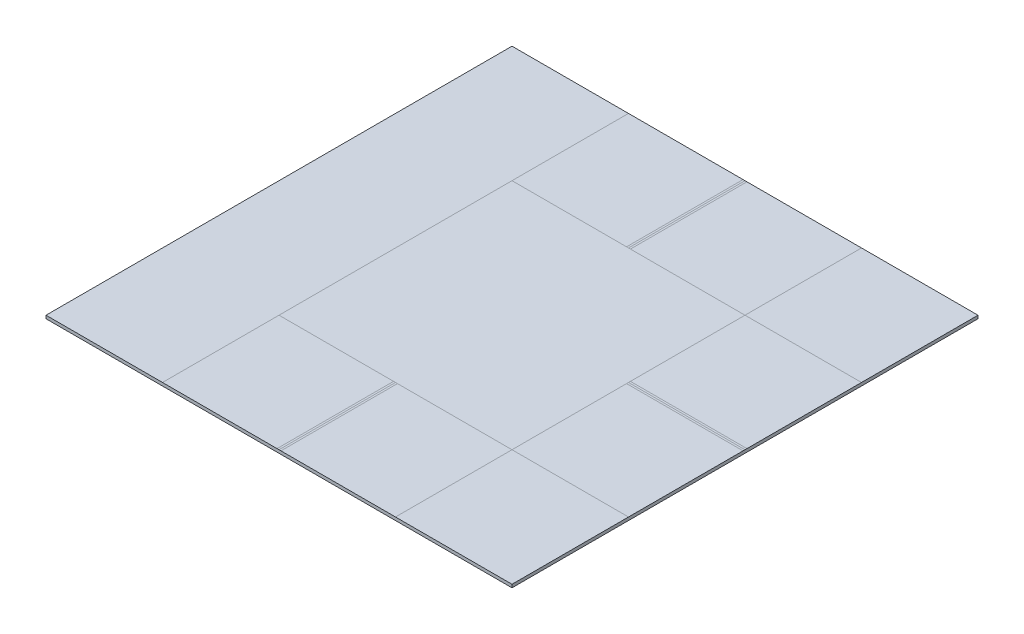
SolidWorks part; units mm, degrees
ref_plane "Front Plane" through (0, 0, 0) normal (0, 0, 1) x (1, 0, 0)
ref_plane "Top Plane" through (0, 0, 0) normal (0, 1, 0) x (1, 0, 0)
ref_plane "Right Plane" through (0, 0, 0) normal (1, 0, 0) x (0, 0, -1)
sketch "Sketch1" plane through (0, 0, 0) normal (0, 1, 0) x (1, 0, 0)
  line L0 (375, -375) -> (750, -750) construction
  line L1 (-750, -750) -> (750, -750)
  line L2 (-750, -750) -> (-750, 750)
  line L3 (-750, 750) -> (750, 750)
  line L4 (750, -750) -> (750, 750)
  line L5 (-750, -750) -> (-375, -375) construction
  line L6 (-750, 750) -> (-375, 375) construction
  line L7 (-375, -750) -> (375, -750)
  line L8 (-375, -750) -> (-375, 750)
  line L9 (-375, 750) -> (375, 750)
  line L10 (375, -750) -> (375, -375)
  line L20 (-750, 442.3995) -> (-750, -307.6005)
  line L27 (375, 375) -> (750, 375)
  line L28 (-750, 375) -> (-750, -375)
  line L29 (375, -375) -> (750, -375)
  line L30 (750, 375) -> (750, -375)
  line L31 (375, 375) -> (750, 750) construction
  line L32 (375, 375) -> (375, 750)
  point P0 (0, 0)
  point P10 (750, 0)
  point P11 (0, 750)
  dimension "D1" = 1500
  dimension "D2" = 750
extrude "Boss-Extrude1" add sketch "Sketch1" along normal blind 10 contours L1 L8 L3 L2 L20 | L27 L32 L3 L8 L1 L10 L29 L4 | L29 L10 L1 L4 | L32 L27 L4 L3 region at (-562.5, 0, 0) region at (112.5, 0, 0) region at (562.5, 0, 562.5) region at (562.5, 0, -562.5)
split line "Split Line5"
sketch "Sketch1<7>" plane through (0, 0, 0) normal (0, 1, 0) x (1, 0, 0) same geometry as "Sketch1"
ref_plane "Plane1" through (-750, 10, -750) normal (1, 0, 0) x (0, 0, -1)
sketch "Sketch3" plane through (0, 10, 0) normal (0, 1, 0) x (1, 0, 0)
  line L0 (375, 375) -> (-375, 375)
  line L1 (-375, -750) -> (-375, 750) construction
  line L2 (0, 375) -> (0, 750)
  line L3 (-375, 750) -> (375, 750) construction
  line L4 (375, -375) -> (-375, -375)
  line L5 (375, 375) -> (375, -375)
  line L6 (0, -375) -> (0, -750)
  line L7 (-375, -750) -> (375, -750) construction
  line L8 (375, 0) -> (750, 0)
  line L9 (750, -375) -> (750, 375) construction
  line L11 (-6.25, -375) -> (6.25, -375)
  line L12 (-6.25, -375) -> (-6.25, -750)
  line L13 (-6.25, -750) -> (6.25, -750)
  line L14 (6.25, -375) -> (6.25, -750)
  line L15 (-6.25, 750) -> (6.25, 750)
  line L16 (-6.25, 750) -> (-6.25, 375)
  line L17 (-6.25, 375) -> (6.25, 375)
  line L18 (6.25, 750) -> (6.25, 375)
  line L19 (375, -6.25) -> (750, -6.25)
  line L20 (375, -6.25) -> (375, 6.25)
  line L21 (375, 6.25) -> (750, 6.25)
  line L22 (750, -6.25) -> (750, 6.25)
  point P24 (0, -750)
  point P29 (0, 750)
  point P34 (750, 0)
  dimension "D1" = 12.5
  dimension "D2" = 12.5
  dimension "D3" = 12.5
split line "Split Line8"
equation "\"Scale\"= 8"
equation "\"Tile Size\"= \"Road Size\" * 2"
equation "\"D1@Sketch1\"=\"Tile Size\""
equation "\"Road Size\"= \"Real Lane Size\" * 2 / \"Scale\""
equation "\"D2@Sketch1\"=\"Road Size\""
equation "\"Real Lane Size\"= 3m"
